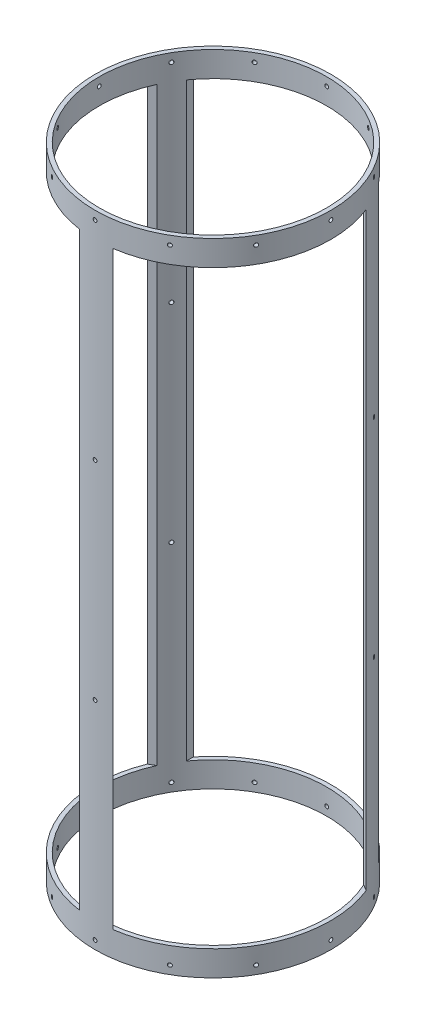
SolidWorks part; units mm, degrees
material "6061-T6 (SS)"
ref_plane "Front Plane" through (0, 0, 0) normal (0, 0, 1) x (1, 0, 0)
ref_plane "Top Plane" through (0, 0, 0) normal (0, 1, 0) x (1, 0, 0)
ref_plane "Right Plane" through (0, 0, 0) normal (1, 0, 0) x (0, 0, -1)
sketch "Sketch1" plane through (0, 0, 0) normal (0, 1, 0) x (1, 0, 0)
  circle A0 centre (0, 0) radius 88.9
  circle A1 centre (0, 0) radius 85.725
  dimension "D1" = 177.8
  dimension "D2" = 171.45
extrude "Boss-Extrude1" add sketch "Sketch1" along normal mid plane 482.854
sketch "Sketch2" plane through (0, 0, 0) normal (0, 0, 1) x (1, 0, 0)
  line L0 (85.725, 241.427) -> (-85.725, 241.427) construction
  line L1 (-69.85, -222.377) -> (69.85, -222.377)
  line L2 (-69.85, -222.377) -> (-69.85, 222.377)
  line L3 (-69.85, 222.377) -> (69.85, 222.377)
  line L4 (69.85, -222.377) -> (69.85, 222.377)
  line L5 (-69.85, -222.377) -> (69.85, 222.377) construction
  line L6 (-69.85, 222.377) -> (69.85, -222.377) construction
  line L7 (88.9, -241.427) -> (88.9, 241.427) construction
  point P0 (0, 0)
  dimension "D1" = 19.05
  dimension "D2" = 19.05
extrude "Cut-Extrude1" cut sketch "Sketch2" against normal up to surface (54.9926 mm away) up to face at (0, 241.427, 88.9)
pattern_circular "CirPattern1" count 3 over 360 about axis through (0, 241.427, 0) along (0, -1, 0) of "Cut-Extrude1"
ref_plane "Plane1" through (88.9, 0, 0) normal (1, 0, 0) x (0, 0, -1)
sketch "Sketch4" plane through (88.9, 0, 0) normal (1, 0, 0) x (0, 0, -1)
  line L0 (0, 97.79) -> (0, -97.79) construction
  line L1 (88.9, 241.427) -> (-88.9, 241.427) construction
  circle A0 centre (0, 235.077) radius 1.4351
  dimension "D1" = 2.8702
  dimension "D2" = 6.35
extrude "Cut-Extrude3" cut sketch "Sketch4" against normal blind 15.24
pattern_circular "CirPattern3" count 12 over 360 about axis through (0, 241.427, 0) along (0, -1, 0) of "Cut-Extrude3"
mirror "Mirror1" about plane through (0, 0, 0) normal (0, 1, 0) of "Cut-Extrude3", "CirPattern3"
ref_plane "Plane2" through (0, 0, 88.9) normal (0, 0, 1) x (1, 0, 0)
sketch "Sketch5" plane through (0, 0, 88.9) normal (0, 0, 1) x (1, 0, 0)
  circle A0 centre (0, 78.359) radius 1.4351
  circle A1 centre (0, -78.359) radius 1.4351
  circle A2 centre (0, -235.077) radius 1.4351 construction
  circle A3 centre (0, 235.077) radius 1.4351 construction
  dimension "D1" = 156.718
  dimension "D2" = 156.718
  dimension "D3" = 2.8702
  dimension "D4" = 2.8702
extrude "Cut-Extrude4" cut sketch "Sketch5" against normal blind 22.86
pattern_circular "CirPattern4" count 3 over 360 about axis through (0, 241.427, 0) along (0, -1, 0) of "Cut-Extrude4"
